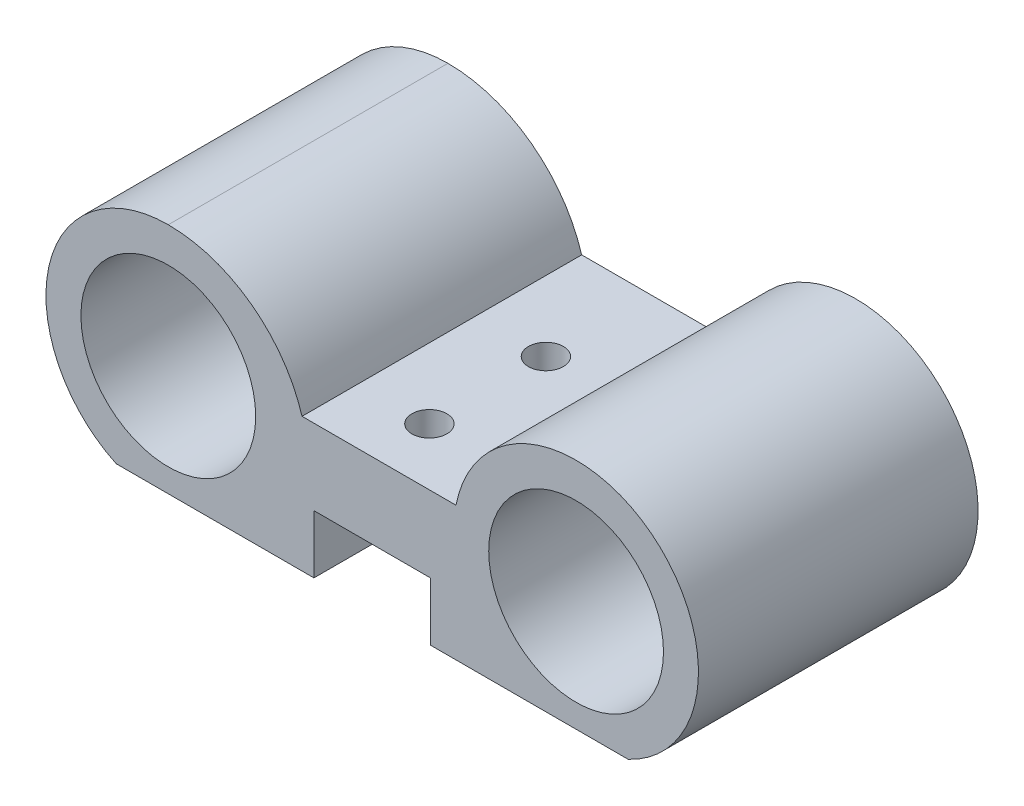
SolidWorks part; units mm, degrees
ref_plane "Front Plane" through (0, 0, 0) normal (0, 0, 1) x (1, 0, 0)
ref_plane "Top Plane" through (0, 0, 0) normal (0, 1, 0) x (1, 0, 0)
ref_plane "Right Plane" through (0, 0, 0) normal (1, 0, 0) x (0, 0, -1)
sketch "Sketch2" plane through (0, 0, 0) normal (0, 0, 1) x (1, 0, 0)
  line L0 (-17.5, 4.5) -> (17.5, 4.5) construction
  line L7 (-17.5, -6) -> (-5, -6)
  line L10 (-6.0218, 6.5) -> (-4.5, 6.5)
  line L14 (-4.5, 6.5) -> (7.1922, 6.5)
  line L19 (5, -6) -> (5, 0)
  line L20 (5, 0) -> (-5, 0)
  line L21 (-5, 0) -> (-5, -6)
  line L23 (5, -6) -> (17.5, -6)
  circle A0 centre (-17.5, 4.5) radius 7.5
  circle A1 centre (17.5, 4.5) radius 7.5
  arc A2 (-17.5, 15) -> (-17.5, -6) centre (-17.5, 4.5) ccw
  arc A3 (17.5, -6) -> (17.5, 15) centre (17.5, 4.5) ccw
  arc A4 (-17.5, 15) -> (-6.0218, 6.5) centre (-17.5, 3) cw
  arc A5 (17.5, 15) -> (7.1922, 6.5) centre (17.5, 4.5) ccw
  point P0 (0, 0)
  point P2 (0, 0)
  point P10 (0, 4.5)
  dimension "D1" = 15
  dimension "D3" = 3
  dimension "D9" = 12
  dimension "D2" = 35
  dimension "D4" = 12.5
  dimension "D5" = 10
  dimension "D6" = 6
extrude "Boss-Extrude1" add sketch "Sketch2" along normal blind 24
sketch "Sketch4" plane through (0, 0, 0) normal (0, -1, 0) x (1, 0, 0)
  line L0 (-5, 0) -> (5, 0) construction
  circle A0 centre (0, 9.091) radius 1.5
  circle A1 centre (0, 19.091) radius 1.5
  dimension "D1" = 3
  dimension "D2" = 9.091
  dimension "D3" = 10
extrude "Cut-Extrude1" cut sketch "Sketch4" against normal blind 10
sketch "Sketch5" plane through (0, 0, 0) normal (0, 0, -1) x (-1, 0, 0)
  line L0 (-5, -6) -> (-17.5, -6) construction
  line L1 (-40.158, -6) -> (28.4592, -6)
  line L2 (-40.158, -6) -> (-40.158, -5)
  line L3 (-40.158, -5) -> (28.4592, -5)
  line L4 (28.4592, -6) -> (28.4592, -5)
  dimension "D1" = 1
extrude "Cut-Extrude2" cut sketch "Sketch5" against normal through all both and the other way through all
